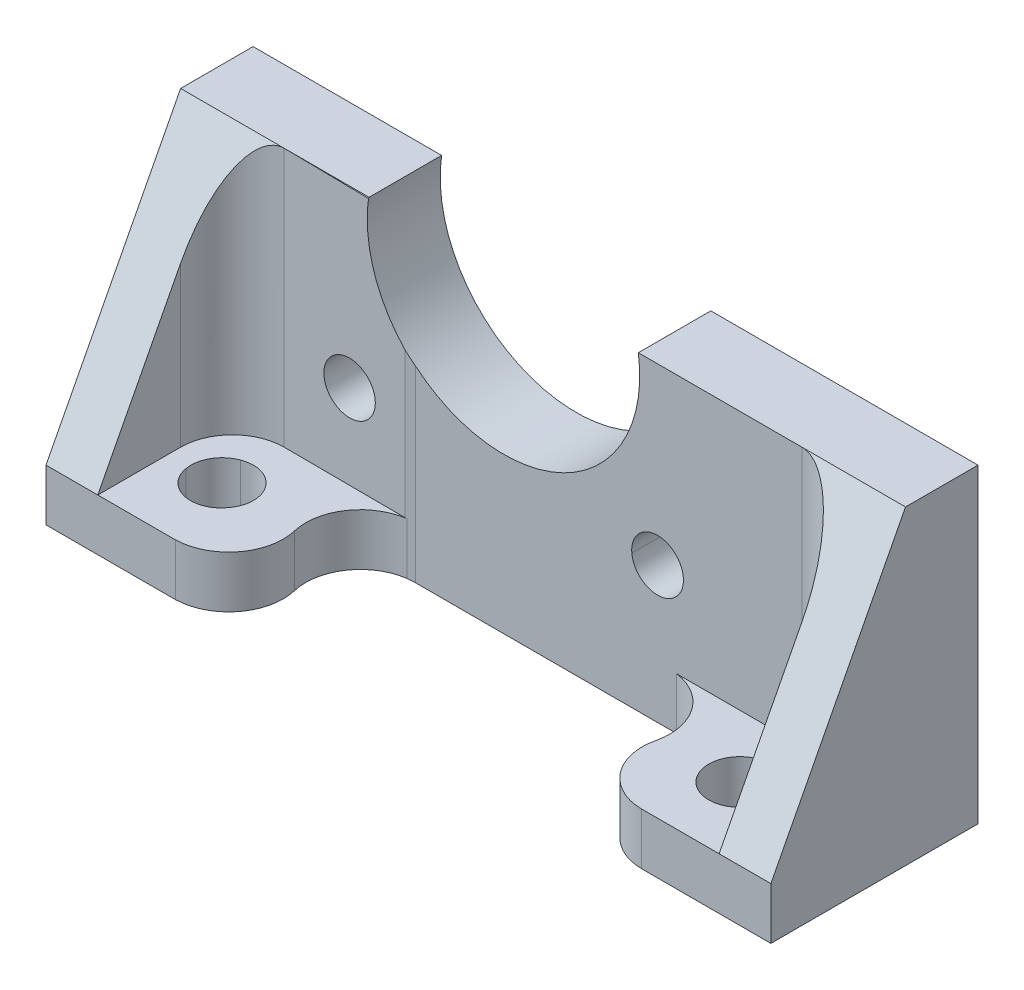
SolidWorks part; units mm, degrees
ref_plane "Front Plane" through (0, 0, 0) normal (0, 0, 1) x (1, 0, 0)
ref_plane "Top Plane" through (0, 0, 0) normal (0, 1, 0) x (1, 0, 0)
ref_plane "Right Plane" through (0, 0, 0) normal (1, 0, 0) x (0, 0, -1)
sketch "Sketch1" plane through (0, 0, 0) normal (0, 0, 1) x (1, 0, 0)
  line L1 (-70, 30) -> (0, 30)
  line L2 (-70, 30) -> (-70, 0)
  line L3 (-70, 0) -> (0, 0)
  line L4 (0, 30) -> (0, 0)
  arc A0 (-44.2, 30) -> (-18.2, 30) centre (-31.2, 28.1333) ccw
  arc A1 (-45.6151, 15.6128) -> (-43.5682, 12.9337) centre (-46.0571, 13.1536) ccw
  arc A2 (-45.6151, 15.6128) -> (-43.5682, 12.9337) centre (-46.0285, 13.1755) cw
  arc A3 (-15.7062, 15.5564) -> (-13.8508, 13.1508) centre (-16.348, 13.1431) ccw
  arc A4 (-15.7062, 15.5564) -> (-13.8508, 13.1508) centre (-16.348, 13.1431) cw
  dimension "D1" = 13.1333
  dimension "D2" = 2.4986
  dimension "D3" = 2.4721
  dimension "D4" = 2.4972
  dimension "D5" = 2.4972
  dimension "D6" = 13.8508
  dimension "D7" = 16.348
  dimension "D8" = 18.2
  dimension "D9" = 31.2
  dimension "D10" = 43.5682
  dimension "D11" = 44.2
  dimension "D12" = 45.6151
  dimension "D13" = 46.0285
  dimension "D14" = 70
  dimension "D15" = 12.9337
  dimension "D16" = 13.1431
  dimension "D17" = 28.1333
  dimension "D18" = 30
extrude "Boss-Extrude1" add sketch "Sketch1" along normal blind 20 contours L1 L4 L3 L2
extrude "Cut-Extrude2" cut sketch "Sketch1<3>" along normal through all contours L1 A0 | A4 A3 | A2 A1 region at (-31.2, 23.5534, 0) region at (-46.0549, 13.1553, 0) region at (-16.348, 13.1431, 0)
sketch "Sketch1<3>" plane through (0, 0, 0) normal (0, 0, 1) x (1, 0, 0) same geometry as "Sketch1"
sketch "Sketch2" plane through (-70, 0, 0) normal (-1, 0, 0) x (0, 0, 1)
  line L0 (0, 30) -> (7, 30)
  line L1 (20, 30) -> (0, 30) construction
  line L2 (20, 0) -> (20, 5)
  line L3 (20, 30) -> (20, 0) construction
  line L4 (7, 30) -> (20, 5)
  line L5 (0, 0) -> (0, 30)
  line L6 (0, 30) -> (0.1732, 29.8857)
  line L7 (7, 30) -> (20, 30)
  line L8 (20, 30) -> (20, 5)
  line M5 (20, 0) -> (20, 30)
  line M6 (20, 30) -> (0, 30)
  dimension "D1" = 7
  dimension "D2" = 5
extrude "Cut-Extrude3" cut sketch "Sketch2" against normal through all contours L4 M6 M5 region at (-70, 21.6667, 15.6667)
sketch "Sketch4" plane through (0, 0, 0) normal (0, 1, 0) x (1, 0, 0)
  line L0 (0, 0) -> (0, -20)
  line L1 (0, 0) -> (70, 0)
  line L2 (70, 0) -> (70, -20)
  line L3 (70, -20) -> (57.5, -20)
  line L4 (0, -20) -> (12.5, -20)
  line L5 (12.5, -20) -> (57.5, -20)
  line L6 (-70, -20) -> (0, -20) construction
  line L7 (-70, 0) -> (0, 0) construction
  line L20 (22.6868, -7) -> (46.4834, -7)
  line L29 (5, -20) -> (5, -12)
  line L30 (22.6868, -7) -> (21.7178, -7.0616)
  line L31 (10, -7) -> (21.7178, -7.0616)
  line L32 (46.4834, -7) -> (60, -7)
  line L33 (65, -20) -> (65, -12)
  arc A0 (12.5, -20) -> (17.5, -13.5) centre (12.3742, -14.7301) ccw
  arc A1 (17.5, -13.5) -> (22.6868, -7) centre (22.6425, -12.2841) cw
  arc A2 (46.4834, -7) -> (52.5, -13.5) centre (47.1822, -12.3878) cw
  arc A3 (52.5, -13.5) -> (57.5, -20) centre (57.575, -14.7692) ccw
  arc A4 (8.9739, -10.1809) -> (12.3742, -14.7301) centre (10.0203, -12.9441) cw
  arc A5 (12.3742, -14.7301) -> (7.0456, -13.5209) centre (9.9551, -13.0449) cw
  arc A6 (8.9739, -10.1809) -> (7.0456, -13.5209) centre (10, -13) ccw
  arc A7 (61.5, -10.4019) -> (61.5, -15.5981) centre (60, -13) cw
  arc A8 (61.5, -10.4019) -> (58.0716, -15.2981) centre (60, -13) ccw
  arc A9 (58.0716, -15.2981) -> (61.5, -15.5981) centre (60, -13) ccw
  arc A10 (5, -12) -> (10, -7) centre (10, -12) cw
  arc A11 (60, -7) -> (65, -12) centre (60, -12) cw
  dimension "D1" = 5.2714
  dimension "D2" = 5.2843
  dimension "D3" = 5.2313
  dimension "D4" = 2.9547
  dimension "D5" = 2.9482
  dimension "D6" = 3
  dimension "D7" = 3
  dimension "D8" = 3
  dimension "D9" = 3
  dimension "D10" = 5
  dimension "D11" = 5
  dimension "D12" = 5
  dimension "D13" = 7.0456
  dimension "D14" = 8.9739
  dimension "D15" = 9.9551
  dimension "D16" = 10.0203
  dimension "D17" = 12.3742
  dimension "D18" = 12.5
  dimension "D19" = 17.5
  dimension "D20" = 21.7178
  dimension "D21" = 22.6425
  dimension "D22" = 22.6868
  dimension "D23" = 52.5
  dimension "D24" = 57.5
  dimension "D25" = 58.0716
  dimension "D26" = 61.5
  dimension "D27" = 65
  dimension "D28" = 70
  dimension "D29" = 7
  dimension "D30" = 7.0616
  dimension "D31" = 10.4019
  dimension "D32" = 20
mirror "Mirror1" about plane through (0, 30, 20) normal (1, 0, 0) of "Boss-Extrude1", "Cut-Extrude3", "Cut-Extrude2"
extrude "Cut-Extrude7" cut sketch "Sketch4" along normal through all contours A3 A2 L32 L20 L30 A1 A0 L5 | A10 L29 L4 A0 A1 L30 L31 A6 A4 A5 | A11 L32 A2 A3 L3 L33 A9 A8 A7 | A5 A6 A4 | A9 A7 A8 region at (5.2135, 0, 16) region at (34.9838, 0, 13.7541) region at (61.25, 0, 19.785)
extrude "Boss-Extrude3" add sketch "Sketch4<6>" along normal blind 5 contours A11 L32 A2 A3 L3 L33 A9 A8 A7 | A10 L29 L4 A0 A1 L30 L31 A6 A4 A5 region at (5.2135, 0, 16) region at (61.25, 0, 19.785)
sketch "Sketch4<6>" plane through (0, 0, 0) normal (0, 1, 0) x (1, 0, 0) same geometry as "Sketch4"
ref_plane "Plane2" through (0, 0, 0) normal (1, 0, 0) x (0, 0, -1)
sketch "Sketch11" plane through (0, 0, 0) normal (1, 0, 0) x (0, 0, -1)
  line L0 (0, 30) -> (-7, 30)
  line L1 (-7, 30) -> (-20, 5)
  line L2 (-20, 5) -> (-20, 0)
  line L3 (-20, 0) -> (0, 0)
  line L4 (0, 0) -> (0, 30)
  line L5 (0, 30) -> (0.1227, 30.1212)
extrude "Cut-Extrude8" cut sketch "Sketch11" against normal through all contours L3 L4 L0 L1 L2 region at (0, 12.5238, 7.8952)
